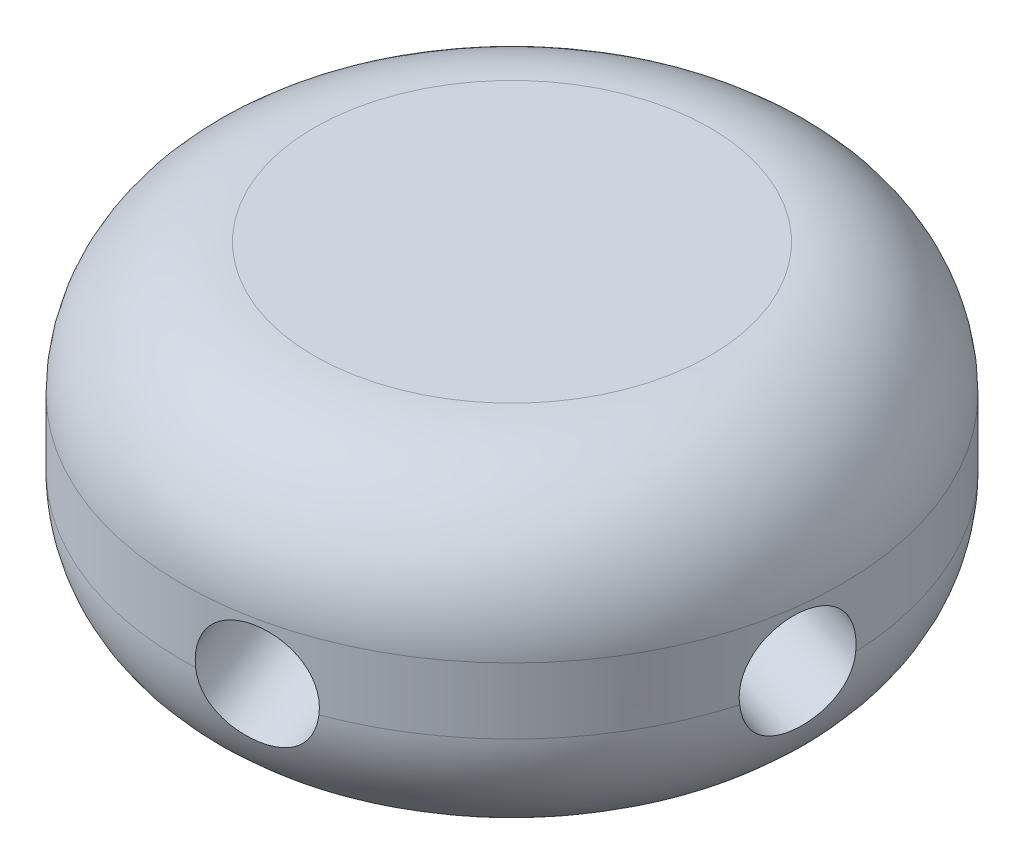
SolidWorks part; units mm, degrees
ref_plane "Front Plane" through (0, 0, 0) normal (0, 0, 1) x (1, 0, 0)
ref_plane "Top Plane" through (0, 0, 0) normal (0, 1, 0) x (1, 0, 0)
ref_plane "Right Plane" through (0, 0, 0) normal (1, 0, 0) x (0, 0, -1)
sketch "Sketch1" plane through (0, 0, 0) normal (0, 1, 0) x (1, 0, 0)
  circle A0 centre (0, 0) radius 10
  dimension "D1" = 20
extrude "Boss-Extrude1" add sketch "Sketch1" along normal blind 3 and the other way blind 7
ref_axis "5hubaxis" through (0, 5.5, 0) along (0, -1, 0)
ref_plane "holeplane" through (-3.3529, -1.0931, 1.8877) normal (0.8382, 0.2733, -0.4719) x (-0.4487, -0.1463, -0.8816)
sketch "Sketch4" plane through (-3.3529, -1.0931, 1.8877) normal (0.8382, 0.2733, -0.4719) x (-0.4487, -0.1463, -0.8816)
  circle A0 centre (0, 0) radius 1.5 construction
  circle A1 centre (0, 0) radius 1.5 construction
  circle A2 centre (0, 0) radius 1.6
  dimension "D1" = 3.2
extrude "hole" cut sketch "Sketch4" against normal through all
pattern_circular "holecir" count 5 over 360 about axis through (0, 5.5, 0) along (0, -1, 0) of "hole"
fillet "Fillet2" radius 4 2 edges at (0, -7, 10) (0, 3, 10)
